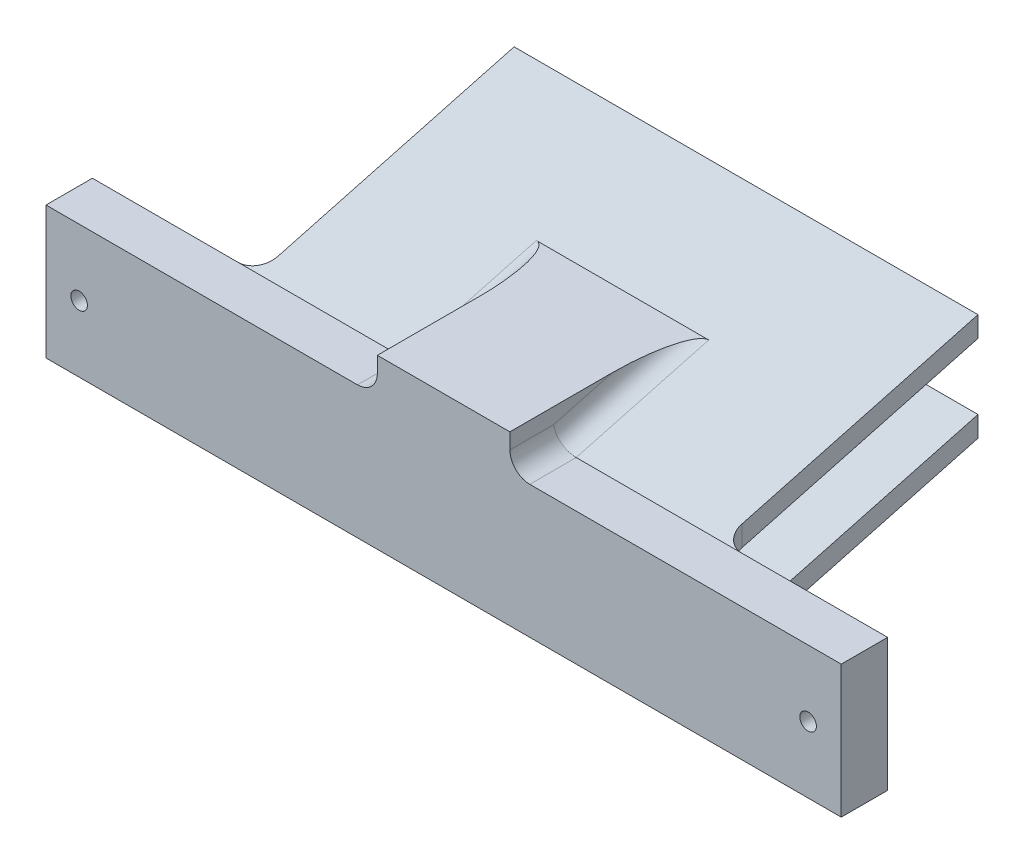
SolidWorks part; units mm, degrees
material "PLA"
ref_plane "Front Plane" through (0, 0, 0) normal (0, 0, 1) x (1, 0, 0)
ref_plane "Top Plane" through (0, 0, 0) normal (0, 1, 0) x (1, 0, 0)
ref_plane "Right Plane" through (0, 0, 0) normal (1, 0, 0) x (0, 0, -1)
sketch "Sketch1" plane through (0, 0, 0) normal (0, 0, 1) x (1, 0, 0)
  line L0 (0, 12.7) -> (0, -12.7) construction
  line L1 (-76.2, -12.7) -> (76.2, -12.7)
  line L2 (-76.2, -12.7) -> (-76.2, 12.7)
  line L3 (-76.2, 12.7) -> (76.2, 12.7)
  line L4 (76.2, -12.7) -> (76.2, 12.7)
  line L5 (-76.2, -12.7) -> (76.2, 12.7) construction
  line L6 (-76.2, 12.7) -> (76.2, -12.7) construction
  circle A0 centre (-69.85, 0) radius 1.5875
  circle A1 centre (69.85, 0) radius 1.5875
  point P0 (0, 0)
  dimension "D3" = 3.175
  dimension "D1" = 152.4
  dimension "D2" = 25.4
  dimension "D4" = 139.7
extrude "Boss-Extrude1" add sketch "Sketch1" along normal blind 8.89
sketch "Sketch2" plane through (0, 0, 0) normal (1, 0, 0) x (0, 0, -1)
  line L0 (0, 0) -> (23.5345, 6.3061) construction
  line L1 (0, -12.7) -> (0, 12.7) construction
  line L2 (0, 8.7556) -> (0, 12.7)
  line L3 (0, 12.7) -> (49.069, 25.848)
  line L4 (49.069, 25.848) -> (49.069, 21.9036)
  line L5 (49.069, 21.9036) -> (0, 8.7556)
  line L6 (0, -3.8665) -> (0, -7.8109)
  line L7 (0, -7.8109) -> (49.069, 5.3371)
  line L8 (49.069, 5.3371) -> (49.069, 9.2815)
  line L9 (49.069, 9.2815) -> (0, -3.8665)
  dimension "D1" = 75
  dimension "D2" = 3.81
  dimension "D3" = 50.8
  dimension "D4" = 3.81
  dimension "D5" = 12.192
  dimension "D6" = 50.8
extrude "Boss-Extrude2" add sketch "Sketch2" along normal mid plane 88.9
sketch "Sketch3" plane through (0, 0, 0) normal (1, 0, 0) x (0, 0, -1)
  line L0 (-8.89, 12.7) -> (-8.89, 19.5059)
  line L1 (-8.89, 19.5059) -> (25.4, 19.5059)
  line L2 (49.069, 25.848) -> (0, 12.7) construction
  line L3 (25.4, 19.5059) -> (0, 12.7)
  line L4 (0, 12.7) -> (-8.89, 12.7)
  line L5 (25.4, -1.005) -> (0, -12.7)
  line L6 (0, -7.8109) -> (49.069, 5.3371) construction
  line L7 (0, -12.7) -> (0, -7.8109)
  line L8 (0, -12.7) -> (0, 12.7) construction
  line L9 (0, -7.8109) -> (25.4, -1.005)
  dimension "D1" = 25.4
  dimension "D2" = 25.4
extrude "Boss-Extrude3" add sketch "Sketch3" along normal mid plane 25.4
fillet "Fillet1" radius 3.81 16 edges at (12.7, 16.103, -12.7) (-12.7, 16.103, -12.7) (44.45, 10.7278, 0) (44.45, -5.8387, 0) (12.7, -4.4079, -12.7) (28.575, -7.8109, 0) (12.7, -10.2554, 0) (-12.7, -4.4079, -12.7) (-12.7, -10.2554, 0) (-28.575, -7.8109, 0) (12.7, 12.7, 4.445) (-12.7, 12.7, 4.445) (-44.45, -5.8387, 0) (-44.45, 10.7278, 0) (0, -3.8665, 0) (0, 8.7556, 0)
